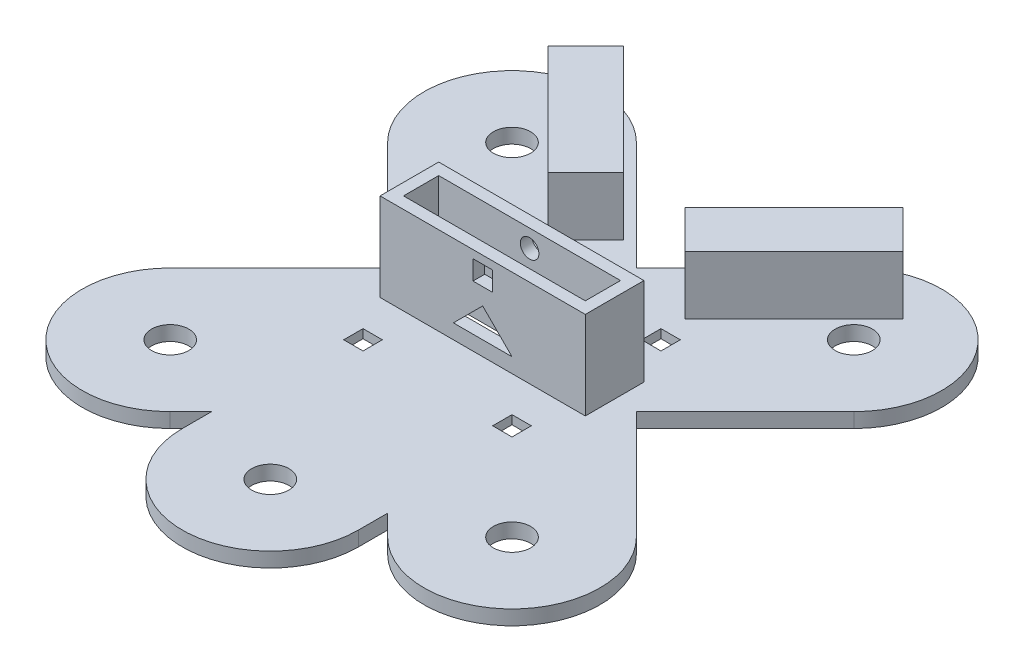
SolidWorks part; units mm, degrees
ref_plane "Front" through (0, 0, 0) normal (0, 0, 1) x (1, 0, 0)
ref_plane "Top" through (0, 0, 0) normal (0, 1, 0) x (1, 0, 0)
ref_plane "Right" through (0, 0, 0) normal (1, 0, 0) x (0, 0, -1)
sketch "Esquisse2" plane through (0, 0, 0) normal (0, 1, 0) x (1, 0, 0)
  line L0 (-30, 30) -> (30, -30) construction
  line L1 (30, 30) -> (30, -30) construction
  line L2 (30, -30) -> (-30, -30) construction
  line L3 (-30, -30) -> (-30, 30) construction
  line L4 (-30, 30) -> (30, 30) construction
  line L5 (30, 30) -> (-30, -30) construction
  line L6 (-1.7157, 1.7157) -> (-58.2843, 58.2843) construction
  line L7 (-22.9289, -19.4975) -> (-79.4975, 37.0711)
  line L8 (19.4975, 22.9289) -> (-37.0711, 79.4975)
  line L11 (5, 11.5685) -> (5, 91.5685) construction
  line L15 (1.7157, 1.7157) -> (58.2843, 58.2843) construction
  line L16 (-19.4975, 22.9289) -> (37.0711, 79.4975)
  line L17 (21.5685, -5) -> (101.5685, -5) construction
  line L20 (22.9289, -19.4975) -> (79.4975, 37.0711)
  line L28 (1.7157, -1.7157) -> (58.2843, -58.2843) construction
  line L29 (-11.5685, -5) -> (-91.5685, -5) construction
  line L30 (22.9289, 19.4975) -> (79.4975, -37.0711)
  line L31 (-19.4975, -22.9289) -> (37.0711, -79.4975)
  line L32 (0, -2.4264) -> (0, -82.4264) construction
  line L33 (30, -2.4264) -> (30, -82.4264)
  line L34 (-30, -2.4264) -> (-30, -82.4264)
  line L35 (-1.7157, -1.7157) -> (-58.2843, -58.2843) construction
  line L36 (19.4975, -22.9289) -> (-37.0711, -79.4975)
  line L37 (-22.9289, 19.4975) -> (-79.4975, -37.0711)
  line L59 (0, 2.4264) -> (0, 82.4264) construction
  line L60 (-30, 2.4264) -> (-30, 82.4264)
  line L61 (30, 2.4264) -> (30, 82.4264)
  line L62 (2.4264, 0) -> (82.4264, 0) construction
  line L63 (2.4264, 30) -> (82.4264, 30)
  line L64 (2.4264, -30) -> (82.4264, -30)
  line L65 (-2.4264, 0) -> (-82.4264, 0) construction
  line L66 (-2.4264, -30) -> (-82.4264, -30)
  line L67 (-2.4264, 30) -> (-82.4264, 30)
  line L68 (0, 2.4264) -> (0, 82.4264) construction
  line L69 (-30, 2.4264) -> (-30, 82.4264)
  line L70 (30, 2.4264) -> (30, 82.4264)
  line L71 (2.4264, 0) -> (82.4264, 0) construction
  line L72 (2.4264, 30) -> (82.4264, 30)
  line L73 (2.4264, -30) -> (82.4264, -30)
  line L74 (-2.4264, 0) -> (-82.4264, 0) construction
  line L75 (-2.4264, -30) -> (-82.4264, -30)
  line L76 (-2.4264, 30) -> (-82.4264, 30)
  arc A0 (-22.9289, -19.4975) -> (19.4975, 22.9289) centre (-1.7157, 1.7157) ccw
  arc A1 (-37.0711, 79.4975) -> (-79.4975, 37.0711) centre (-58.2843, 58.2843) ccw
  arc A6 (-19.4975, 22.9289) -> (22.9289, -19.4975) centre (1.7157, 1.7157) ccw
  arc A7 (79.4975, 37.0711) -> (37.0711, 79.4975) centre (58.2843, 58.2843) ccw
  arc A16 (22.9289, 19.4975) -> (-19.4975, -22.9289) centre (1.7157, -1.7157) ccw
  arc A17 (37.0711, -79.4975) -> (79.4975, -37.0711) centre (58.2843, -58.2843) ccw
  arc A18 (30, -2.4264) -> (-30, -2.4264) centre (0, -2.4264) ccw
  arc A19 (-30, -82.4264) -> (30, -82.4264) centre (0, -82.4264) ccw
  arc A20 (19.4975, -22.9289) -> (-22.9289, 19.4975) centre (-1.7157, -1.7157) ccw
  arc A21 (-79.4975, -37.0711) -> (-37.0711, -79.4975) centre (-58.2843, -58.2843) ccw
  arc A42 (-30, 2.4264) -> (30, 2.4264) centre (0, 2.4264) ccw
  arc A43 (30, 82.4264) -> (-30, 82.4264) centre (0, 82.4264) ccw
  arc A44 (2.4264, 30) -> (2.4264, -30) centre (2.4264, 0) ccw
  arc A45 (82.4264, -30) -> (82.4264, 30) centre (82.4264, 0) ccw
  arc A46 (-2.4264, -30) -> (-2.4264, 30) centre (-2.4264, 0) ccw
  arc A47 (-82.4264, 30) -> (-82.4264, -30) centre (-82.4264, 0) ccw
  point P0 (0, 0)
  point P9 (-30, 30)
  point P19 (5, 51.5685)
  point P22 (0, 49.4975)
  point P29 (30, 30)
  point P33 (61.5685, -5)
  point P39 (49.4975, 0)
  point P46 (30, -30)
  point P53 (0, -42.4264)
  point P61 (-51.5685, -5)
  point P63 (-30, -30)
  point P66 (5, -5)
  point P71 (-49.4975, 0)
  point P76 (0, 0)
  point P109 (0, 49.4975)
  point P116 (49.4975, 0)
  point P123 (-49.4975, 0)
  point P130 (0, 42.4264)
  point P137 (42.4264, 0)
  point P144 (-42.4264, 0)
  point P151 (0, 42.4264)
  point P158 (42.4264, 0)
  point P165 (-42.4264, 0)
  point P172 (0, 42.4264)
  point P179 (42.4264, 0)
  point P186 (-42.4264, 0)
  dimension "D4" = 30
  dimension "D1" = 60
  dimension "D2" = 60
  dimension "D3" = 80
  dimension "D5" = 8
extrude "Boss.-Extru.1" add sketch "Esquisse2" along normal blind 5 contours A17 | L36 A21 L37 A20 | L33 A19 L34 A18 | L30 A17 L31 A16 | L8 A1 L7 A0 | L16 A7 L20 A6
sketch "Esquisse4" plane through (0, 0, 0) normal (0, -1, 0) x (-1, 0, 0)
  line L0 (0, 0) -> (-79.4975, -79.4975) construction
  line L1 (-25.317, -46.5302) -> (-7.6393, -28.8525)
  line L2 (-7.6393, -28.8525) -> (-28.8525, -7.6393)
  line L3 (-28.8525, -7.6393) -> (-46.5302, -25.317)
  line L4 (-42.4264, 0) -> (-79.4975, -37.0711) construction
  line L5 (-46.5302, 25.317) -> (-28.8525, 7.6393)
  line L6 (-7.6393, 28.8525) -> (-25.317, 46.5302)
  line L7 (-28.8525, 7.6393) -> (-7.6393, 28.8525)
  line L8 (25.317, 46.5302) -> (7.6393, 28.8525)
  line L9 (28.8525, 7.6393) -> (46.5302, 25.317)
  line L10 (7.6393, 28.8525) -> (28.8525, 7.6393)
  line L11 (46.5302, -25.317) -> (28.8525, -7.6393)
  line L12 (7.6393, -28.8525) -> (25.317, -46.5302)
  line L13 (28.8525, -7.6393) -> (7.6393, -28.8525)
  arc A0 (-79.4975, -37.0711) -> (-37.0711, -79.4975) centre (-58.2843, -58.2843) ccw construction
  arc A1 (-25.317, -46.5302) -> (-46.5302, -25.317) centre (-58.2843, -58.2843) ccw
  arc A2 (-46.5302, 25.317) -> (-25.317, 46.5302) centre (-58.2843, 58.2843) ccw
  arc A3 (25.317, 46.5302) -> (46.5302, 25.317) centre (58.2843, 58.2843) ccw
  arc A4 (46.5302, -25.317) -> (25.317, -46.5302) centre (58.2843, -58.2843) ccw
  point P36 (0, 0)
  dimension "D5" = 35
  dimension "D1" = 25
  dimension "D2" = 25
  dimension "D3" = 15
  dimension "D4" = 30
extrude "Enlèv. mat.-Extru.1" cut sketch "Esquisse4" against normal blind 2 contours L0 L2 L3 A1 | L2 L0 A1 L1 | A2 L5 L7 L6 | A3 L8 L10 L9 | A4 L11 L13 L12 region at (20.863, 0, 31.7295) region at (31.7295, 0, 20.863) region at (26.2963, 0, -26.2963) region at (-26.2963, 0, -26.2963) region at (-26.2963, 0, 26.2963)
sketch "Esquisse7" plane through (0, 0, 0) normal (0, -1, 0) x (-1, 0, 0)
  circle A0 centre (0, -82.4264) radius 6.35
  circle A1 centre (-58.2843, -58.2843) radius 6.35
  circle A2 centre (-82.4264, 0) radius 6.35 [skipped]
  circle A3 centre (-58.2843, 58.2843) radius 6.35
  circle A4 centre (0, 82.4264) radius 6.35 [skipped]
  circle A5 centre (58.2843, 58.2843) radius 6.35
  circle A6 centre (82.4264, 0) radius 6.35 [skipped]
  circle A7 centre (58.2843, -58.2843) radius 6.35
  point P20 (0, 0)
  dimension "D1" = 12.7
extrude "Enlèv. mat.-Extru.3" cut sketch "Esquisse7" against normal through all
sketch "Esquisse10" plane through (0, 5, 0) normal (0, 1, 0) x (1, 0, 0)
  line L0 (58.2843, -58.2843) -> (0, 0) construction
  circle A0 centre (25.4038, -25.4038) radius 3.175
  circle A1 centre (-25.4038, -25.4038) radius 3.175
  circle A2 centre (-25.4038, 25.4038) radius 3.175
  circle A3 centre (25.4038, 25.4038) radius 3.175
  point P15 (0, 0)
  dimension "D1" = 6.35
  dimension "D2" = 46.5
extrude "Enlèv. mat.-Extru.4" cut sketch "Esquisse10" against normal through all
sketch "Esquisse11" plane through (0, 5, 0) normal (0, 1, 0) x (1, 0, 0)
  line L0 (-22.1038, -28.7038) -> (-28.7038, -28.7038)
  line L1 (28.7038, -22.1038) -> (22.1038, -22.1038)
  line L2 (28.7038, -22.1038) -> (28.7038, -28.7038)
  line L3 (28.7038, -28.7038) -> (22.1038, -28.7038)
  line L4 (22.1038, -22.1038) -> (22.1038, -28.7038)
  line L5 (28.7038, -22.1038) -> (22.1038, -28.7038) construction
  line L6 (28.7038, -28.7038) -> (22.1038, -22.1038) construction
  line L7 (-22.1038, -28.7038) -> (-22.1038, -22.1038)
  line L8 (-22.1038, -22.1038) -> (-28.7038, -22.1038)
  line L9 (-28.7038, -28.7038) -> (-28.7038, -22.1038)
  line L10 (-28.7038, 22.1038) -> (-28.7038, 28.7038)
  line L11 (-28.7038, 22.1038) -> (-22.1038, 22.1038)
  line L12 (-22.1038, 22.1038) -> (-22.1038, 28.7038)
  line L13 (-28.7038, 28.7038) -> (-22.1038, 28.7038)
  line L14 (22.1038, 28.7038) -> (28.7038, 28.7038)
  line L15 (22.1038, 28.7038) -> (22.1038, 22.1038)
  line L16 (22.1038, 22.1038) -> (28.7038, 22.1038)
  line L17 (28.7038, 28.7038) -> (28.7038, 22.1038)
  point P0 (25.4038, -25.4038)
  point P21 (0, 0)
  dimension "D1" = 6.6
  dimension "D2" = 6.6
extrude "Enlèv. mat.-Extru.5" cut sketch "Esquisse11" against normal blind 3.5
sketch "Esquisse16" plane through (0, 5, 0) normal (0, 1, 0) x (1, 0, 0)
  line L0 (47.7021, 85.6982) -> (10.478, 48.4742)
  line L1 (10.478, 48.4742) -> (23.3404, 35.6118)
  line L2 (23.3404, 35.6118) -> (60.5645, 72.8359)
  line L3 (60.5645, 72.8359) -> (47.7021, 85.6982)
  line L4 (0, -50) -> (0, 50) construction
  line L5 (-23.3404, 35.6118) -> (-60.5645, 72.8359)
  line L6 (-10.478, 48.4742) -> (-23.3404, 35.6118)
  line L7 (-47.7021, 85.6982) -> (-10.478, 48.4742)
  line L8 (-60.5645, 72.8359) -> (-47.7021, 85.6982)
extrude "Boss.-Extru.8" add sketch "Esquisse16" along normal blind 20
sketch "Esquisse18" plane through (0, 5, 0) normal (0, 1, 0) x (1, 0, 0)
  line L1 (-35, 10) -> (35, 10)
  line L2 (-35, 10) -> (-35, -10)
  line L3 (-35, -10) -> (35, -10)
  line L4 (35, 10) -> (35, -10)
  line L5 (-35, 10) -> (35, -10) construction
  line L6 (-35, -10) -> (35, 10) construction
  line L7 (-31, 6) -> (31, 6)
  line L8 (-31, 6) -> (-31, -6)
  line L9 (-31, -6) -> (31, -6)
  line L10 (31, 6) -> (31, -6)
  line L11 (-31, 6) -> (31, -6) construction
  line L12 (-31, -6) -> (31, 6) construction
  point P0 (0, 0)
  point P6 (0, 0)
  dimension "D1" = 20
  dimension "D2" = 70
  dimension "D3" = 62
  dimension "D4" = 12
extrude "Boss.-Extru.9" add sketch "Esquisse18" along normal blind 30
sketch "Esquisse19" plane through (0, 0, 10) normal (0, 0, 1) x (1, 0, 0)
  line L0 (-35, 35) -> (35, 35) construction
  line L1 (35, 35) -> (35, 5) construction
  circle A0 centre (0, 29) radius 3.175
  dimension "D1" = 6.35
  dimension "D2" = 6
  dimension "D3" = 35
extrude "Enlèv. mat.-Extru.6" cut sketch "Esquisse19" against normal through all
sketch "Esquisse20" plane through (0, 0, 10) normal (0, 0, 1) x (1, 0, 0)
  line L1 (-3.3, 32.3) -> (3.3, 32.3)
  line L2 (-3.3, 32.3) -> (-3.3, 25.7)
  line L3 (-3.3, 25.7) -> (3.3, 25.7)
  line L4 (3.3, 32.3) -> (3.3, 25.7)
  line L5 (-3.3, 32.3) -> (3.3, 25.7) construction
  line L6 (-3.3, 25.7) -> (3.3, 32.3) construction
  point P0 (0, 29)
  dimension "D1" = 6.6
  dimension "D2" = 6.6
extrude "Enlèv. mat.-Extru.7" cut sketch "Esquisse20" against normal blind 4
sketch "Esquisse21" plane through (0, 5, 0) normal (0, 1, 0) x (1, 0, 0)
  line L1 (-20, -5) -> (20, -5)
  line L2 (-20, -5) -> (-20, 5)
  line L3 (-20, 5) -> (20, 5)
  line L4 (20, -5) -> (20, 5)
  line L5 (-20, -5) -> (20, 5) construction
  line L6 (-20, 5) -> (20, -5) construction
  point P0 (0, 0)
  dimension "D1" = 10
  dimension "D2" = 40
extrude "Enlèv. mat.-Extru.8" cut sketch "Esquisse21" against normal through all
sketch "Esquisse22" plane through (0, 0, -10) normal (0, 0, -1) x (-1, 0, 0)
  line L0 (-10, 10) -> (10, 10)
  line L1 (10, 10) -> (0, 20)
  line L2 (0, 20) -> (-10, 10)
  line L3 (35, 35) -> (35, 5) construction
  line L4 (-35, 5) -> (35, 5) construction
  point P2 (0, 0)
  dimension "D1" = 45
  dimension "D2" = 45
  dimension "D3" = 20
  dimension "D4" = 35
  dimension "D5" = 5
extrude "Enlèv. mat.-Extru.9" cut sketch "Esquisse22" against normal through all
